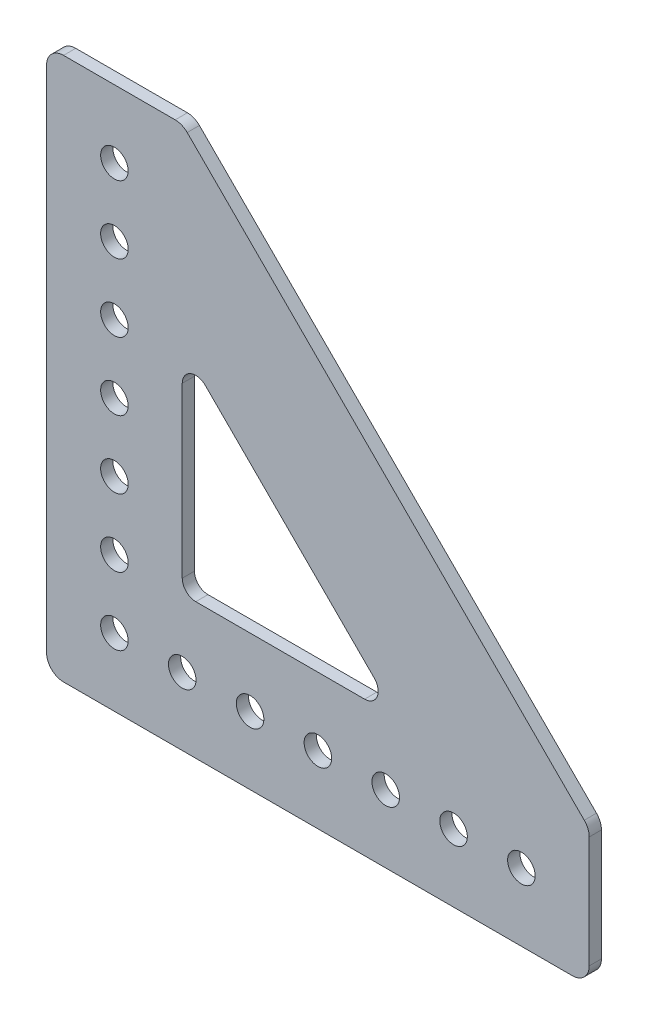
SolidWorks part; units mm, degrees
ref_plane "Front Plane" through (0, 0, 0) normal (0, 0, 1) x (1, 0, 0)
ref_plane "Top Plane" through (0, 0, 0) normal (0, 1, 0) x (1, 0, 0)
ref_plane "Right Plane" through (0, 0, 0) normal (1, 0, 0) x (0, 0, -1)
sketch "Sketch1" plane through (0, 0, 0) normal (0, 0, 1) x (1, 0, 0)
  line L0 (43.0463, -67.5105) -> (43.0463, -42.1105)
  line L1 (-58.5537, 34.0895) -> (-33.1537, 34.0895)
  line L2 (-58.5537, 34.0895) -> (-58.5537, -67.5105)
  line L3 (-58.5537, -67.5105) -> (43.0463, -67.5105)
  line L4 (-45.8537, 34.0895) -> (-45.8537, -67.5105) construction
  line L5 (0, 0) -> (38.8723, -37.9365) construction
  line L6 (-58.5537, -67.5105) -> (0.4347, 0.5011) construction
  line L7 (43.0463, -42.1105) -> (-33.1537, 34.0895)
  circle A0 centre (-45.8537, 21.3895) radius 2.5781
  circle A1 centre (-45.8537, 8.6895) radius 2.5781
  circle A2 centre (-45.8537, -4.0105) radius 2.5781
  circle A3 centre (-45.8537, -16.7105) radius 2.5781
  circle A4 centre (-33.1537, -54.8105) radius 2.5781
  circle A5 centre (-20.4537, -54.8105) radius 2.5781
  circle A6 centre (-7.7537, -54.8105) radius 2.5781
  circle A7 centre (-45.8537, -29.4105) radius 2.5781
  circle A8 centre (-45.8537, -42.1105) radius 2.5781
  circle A9 centre (-45.8537, -54.8105) radius 2.5781
  circle A10 centre (4.9463, -54.8105) radius 2.5781
  circle A11 centre (17.6463, -54.8105) radius 2.5781
  circle A12 centre (30.3463, -54.8105) radius 2.5781
  point P0 (0, 0)
  dimension "D8" = 5.1562
  dimension "D1" = 25.4
  dimension "D2" = 25.4
  dimension "D3" = 101.6
  dimension "D4" = 101.6
  dimension "D5" = 12.7
  dimension "D6" = 7
  dimension "D7" = 7
extrude "Boss-Extrude1" add sketch "Sketch1" along normal mid plane 2.286
fillet "Fillet1" radius 3.175 5 edges at (-58.5537, 34.0895, 0) (43.0463, -42.1105, 0) (43.0463, -67.5105, 0) (-58.5537, -67.5105, 0) (-33.1537, 34.0895, 0)
sketch "Sketch2" plane through (0, 0, 1.143) normal (0, 0, 1) x (1, 0, 0)
  line L16 (-33.1537, -1.8316) -> (-33.1537, -42.1105)
  line L17 (-33.1537, -42.1105) -> (7.1253, -42.1105)
  line L18 (7.1253, -42.1105) -> (-33.1537, -1.8316)
  line L19 (-33.1537, -7.9637) -> (-33.1537, -39.5705)
  line L20 (-30.6137, -42.1105) -> (0.9932, -42.1105)
  line L21 (2.7892, -37.7745) -> (-28.8176, -6.1676)
  arc A10 (-30.6137, -42.1105) -> (-33.1537, -39.5705) centre (-30.6137, -39.5705) cw
  arc A11 (0.9932, -42.1105) -> (2.7892, -37.7745) centre (0.9932, -39.5705) ccw
  arc A12 (-28.8176, -6.1676) -> (-33.1537, -7.9637) centre (-30.6137, -7.9637) ccw
  dimension "D2" = 2.54
  dimension "D1" = 25.4
extrude "Cut-Extrude1" cut sketch "Sketch2" against normal blind 2.54
